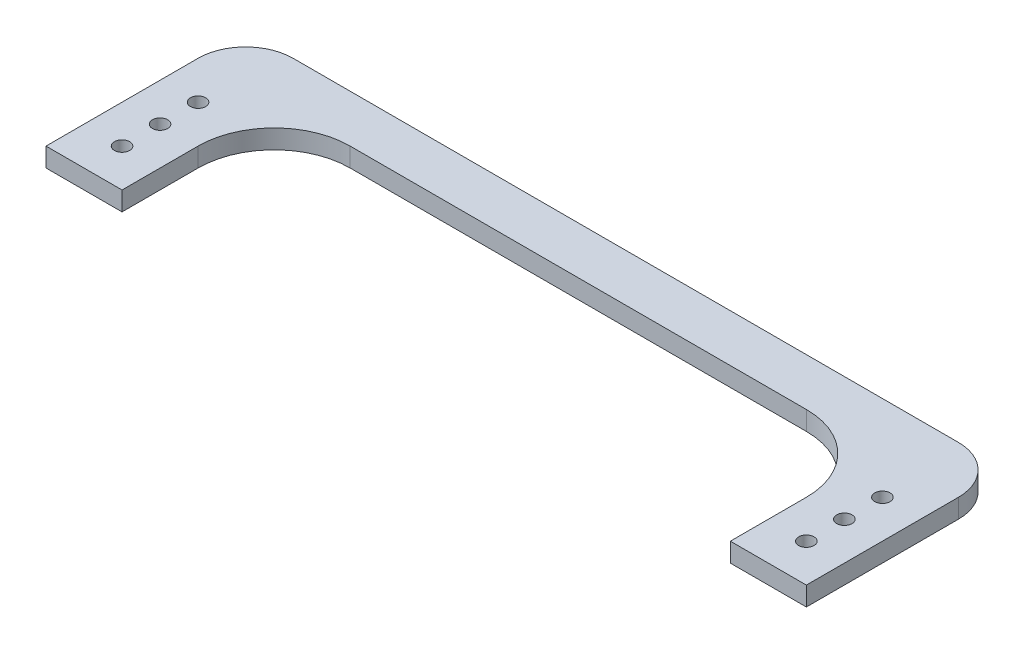
SolidWorks part; units mm, degrees
material "6061-T6 (SS)"
ref_plane "Front" through (0, 0, 0) normal (0, 0, 1) x (1, 0, 0)
ref_plane "Top" through (0, 0, 0) normal (0, 1, 0) x (1, 0, 0)
ref_plane "Right" through (0, 0, 0) normal (1, 0, 0) x (0, 0, -1)
sketch "Sketch1" plane through (0, 0, 0) normal (0, 1, 0) x (1, 0, 0)
  line L0 (-101.6, -25.4) -> (-101.6, 0)
  line L1 (101.6, 0) -> (101.6, -25.4)
  line L2 (101.6, -25.4) -> (127, -25.4)
  line L3 (0, 0) -> (0, -66.2098) construction
  line L4 (-101.6, -25.4) -> (-127, -25.4)
  line L5 (-127, -25.4) -> (-127, 25.4)
  line L6 (127, 25.4) -> (127, -25.4)
  line L8 (-76.2, 25.4) -> (76.2, 25.4)
  line L12 (111.125, 41.275) -> (-111.125, 41.275)
  line L14 (127, 6.8059) -> (127, -25.4) construction
  line L15 (-127, -25.4) -> (-127, 6.8059) construction
  arc A6 (85.728, 9.9217) -> (101.6, 0) centre (81.1476, -15.0619) cw construction
  arc A7 (-127, 6.8059) -> (-87.8514, 57.3252) centre (57.0959, -95.4263) cw construction
  arc A8 (-87.8514, 57.3252) -> (90.3083, 34.9053) centre (-198.2524, -1539.0619) cw construction
  arc A9 (90.3083, 34.9053) -> (127, 6.8059) centre (81.1476, -15.0619) cw construction
  arc A10 (-101.6, 0) -> (-78.0712, 31.1456) centre (57.0959, -95.4263) cw construction
  arc A11 (-78.0712, 31.1456) -> (85.728, 9.9217) centre (-198.2524, -1539.0619) cw construction
  arc A13 (127, 25.4) -> (111.125, 41.275) centre (111.125, 25.4) ccw
  arc A15 (-111.125, 41.275) -> (-127, 25.4) centre (-111.125, 25.4) ccw
  arc A16 (76.2, 25.4) -> (101.6, 0) centre (76.2, 0) cw
  arc A17 (-101.6, 0) -> (-76.2, 25.4) centre (-76.2, 0) cw
  dimension "D9" = 25.4
  dimension "D1" = 203.2
  dimension "D2" = 50.8
  dimension "D6" = 15.875
  dimension "D3" = 25.4
extrude "Boss-Extrude1" add sketch "Sketch1" along normal blind 6.35
hole_wizard "#10 Clearance Hole1" positions "Sketch2" profile "Sketch3" hole size "#10" standard "ANSI Inch" end condition through all
sketch "Sketch2" plane through (0, 6.35, 0) normal (0, 1, 0) x (1, 0, 0)
  line L3 (-127, -25.4) -> (-114.3, -12.7) construction
  line L4 (-114.3, -12.7) -> (-114.3, 0) construction
  line L5 (-114.3, 0) -> (-114.3, 12.7) construction
  line L6 (-114.3, 12.7) -> (-101.6, 25.4) construction
  line L8 (0, 0) -> (0, -50.8) construction
  line L9 (-101.6, -25.4) -> (-101.6, 0) construction
  line L10 (-76.2, 25.4) -> (76.2, 25.4) construction
  point P0 (-114.3, -12.7)
  point P2 (-114.3, 0)
  point P4 (-114.3, 12.7)
  point P29 (114.3, 12.7)
  point P30 (114.3, 0)
  point P31 (114.3, -12.7)
  dimension "D1" = 12.7
sketch "Sketch3" plane through (-114.3, 6.35, 12.7) normal (1, 0, 0) x (0, 0, 1)
  line L0 (0, 0) -> (0, 6.35)
  line L1 (0, 6.35) -> (2.5527, 6.35)
  line L2 (2.5527, 6.35) -> (2.5527, 0)
  line L5 (2.5527, 0) -> (0, 0)
  line L11 (0, -6.35) -> (0, 107.95) construction
  dimension "Thru Hole Dia." = 5.1054
  dimension "Thru Hole Depth" = 6.35
